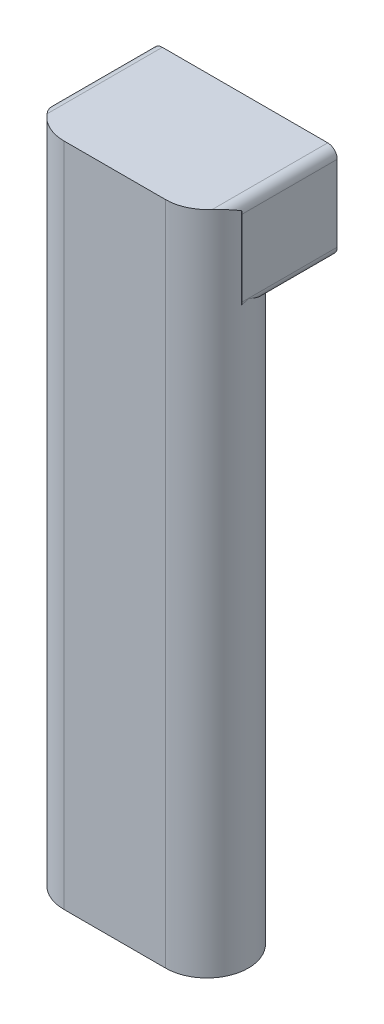
SolidWorks part; units mm, degrees
ref_plane "Спереди" through (0, 0, 0) normal (0, 0, 1) x (1, 0, 0)
ref_plane "Сверху" through (0, 0, 0) normal (0, 1, 0) x (1, 0, 0)
ref_plane "Справа" through (0, 0, 0) normal (1, 0, 0) x (0, 0, -1)
sketch "Эскиз1" plane through (0, 0, 0) normal (0, 1, 0) x (1, 0, 0)
  line L0 (-0.535, 0.435) -> (0.535, 0.4349)
  line L1 (-0.535, -0.435) -> (0.535, -0.4349)
  circle A0 centre (-0.535, 0) radius 0.26
  circle A1 centre (0.535, 0) radius 0.26
  arc A4 (-0.535, 0.435) -> (-0.535, -0.435) centre (-0.535, 0) ccw
  arc A5 (0.535, 0.4349) -> (0.535, -0.4349) centre (0.535, 0) cw
  dimension "D1" = 0.52
  dimension "D2" = 0.52
  dimension "D5" = 1.07
  dimension "D3" = 0.535
extrude "Бобышка-Вытянуть1" add sketch "Эскиз1" along normal blind 6
sketch "Эскиз2" plane through (0, 6, 0) normal (0, 1, 0) x (1, 0, 0)
  line L2 (-0.535, -0.435) -> (0.535, -0.4349)
  line L3 (0.535, 0.4349) -> (-0.535, 0.435)
  line L4 (-0.535, -0.435) -> (0.535, -0.4349)
  line L5 (0.535, 0.4349) -> (-0.535, 0.435)
  arc A2 (-0.535, 0.435) -> (-0.535, -0.435) centre (-0.535, 0) ccw
  arc A3 (0.535, -0.4349) -> (0.535, 0.4349) centre (0.535, 0) ccw
  arc A4 (-0.535, 0.435) -> (-0.535, -0.435) centre (-0.535, 0) ccw
  arc A5 (0.535, -0.4349) -> (0.535, 0.4349) centre (0.535, 0) ccw
  dimension "D1" = 0
sketch "Эскиз3" plane through (0, 6, 0) normal (0, 1, 0) x (1, 0, 0)
  line L2 (-0.535, -0.435) -> (0.535, -0.4349)
  line L3 (0.535, 0.4349) -> (-0.535, 0.435)
  line L4 (-0.535, -0.435) -> (0.535, -0.4349)
  line L5 (0.535, 0.4349) -> (-0.535, 0.435)
  arc A2 (-0.535, 0.435) -> (-0.535, -0.435) centre (-0.535, 0) ccw
  arc A3 (0.535, -0.4349) -> (0.535, 0.4349) centre (0.535, 0) ccw
  arc A4 (-0.535, 0.435) -> (-0.535, -0.435) centre (-0.535, 0) ccw
  arc A5 (0.535, -0.4349) -> (0.535, 0.4349) centre (0.535, 0) ccw
  dimension "D1" = 0
extrude "Бобышка-Вытянуть2" add sketch "Эскиз3" along normal blind 1
sketch "Эскиз4" plane through (0, 0, -0.4349) normal (0.0001, 0, -1) x (-1, 0, -0.0001)
  line L0 (-0.535, 7) -> (0.535, 6) construction
  line L1 (0.97, 6) -> (0.535, 6) construction
  line L2 (0.535, 7) -> (0.535, 0) construction
  line L3 (0.535, 7) -> (-0.535, 6) construction
  line L4 (-0.535, 6) -> (-0.9699, 6) construction
  line L5 (0.535, 6) -> (-0.535, 6) construction
  line L6 (0, 6.5) -> (-0.535, 6.5) construction
  line L7 (-0.535, 7) -> (-0.535, 0) construction
  line L8 (0, 6.5) -> (0.535, 6.5) construction
  line L14 (-0.97, 6) -> (0.97, 6)
  line L15 (-0.97, 6) -> (-0.97, 7)
  line L16 (-0.97, 7) -> (0.97, 7)
  line L17 (0.97, 6) -> (0.97, 7)
  line L18 (-0.97, 6) -> (0.97, 7) construction
  line L19 (-0.97, 7) -> (0.97, 6) construction
  circle A0 centre (-0.5, 6.5) radius 0.4
  circle A1 centre (0.5, 6.5) radius 0.4
  dimension "D1" = 0.5
  dimension "D3" = 0.8
  dimension "D4" = 0.8
  dimension "D2" = 1
extrude "Бобышка-Вытянуть3" add sketch "Эскиз4" along normal blind 0.5
extrude "Бобышка-Вытянуть4" add sketch "Эскиз4<2>" against normal blind 0.5
sketch "Эскиз4<2>" plane through (0, 0, -0.4349) normal (0.0001, 0, -1) x (-1, 0, -0.0001) same geometry as "Эскиз4"
fillet "Скругление1" radius 0.1 4 edges at (-0.97, 6, -0.435) (-0.97, 7, -0.435) (0.97, 6, -0.4349) (0.97, 7, -0.4349)
